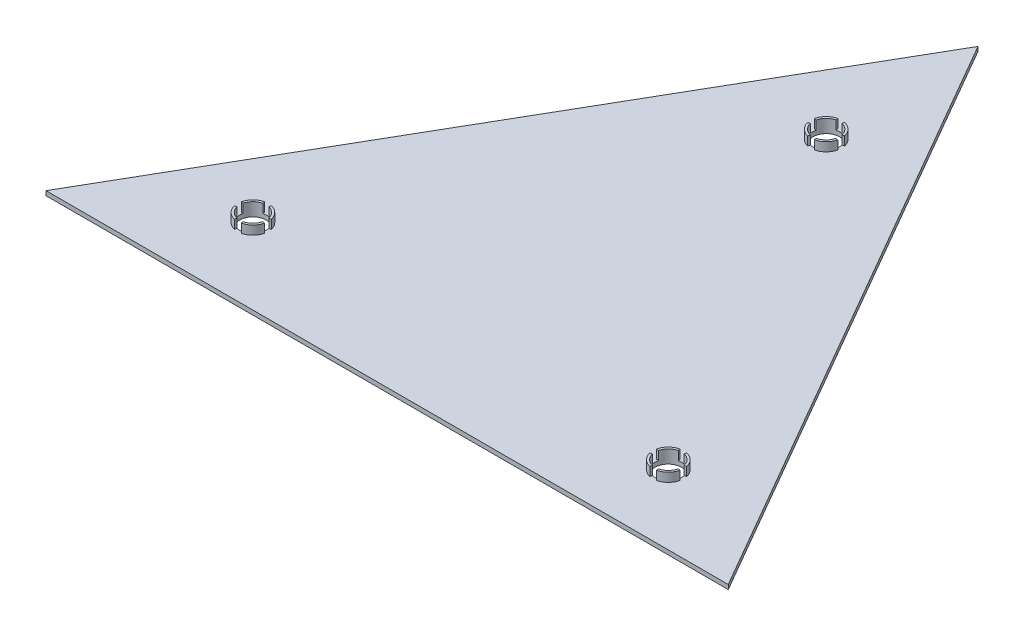
SolidWorks part; units mm, degrees
note: The reader was unsure of these and kept them because the rebuilt part matched: shared geometry of "Sketch1<15>".
ref_plane "Front Plane" through (0, 0, 0) normal (0, 0, 1) x (1, 0, 0)
ref_plane "Top Plane" through (0, 0, 0) normal (0, 1, 0) x (1, 0, 0)
ref_plane "Right Plane" through (0, 0, 0) normal (1, 0, 0) x (0, 0, -1)
sketch "Sketch1" plane through (0, 0, 0) normal (0, 1, 0) x (1, 0, 0)
  line L1 (363.2501, -12.5071) -> (363.2501, -12.0071) construction
  line L2 (363.2501, -12.0071) -> (364.0231, -12.0935) construction
  line L7 (364.0231, -12.0935) -> (363.9127, -12.5812)
  line L8 (363.2501, -12.0071) -> (362.4772, -12.0935) construction
  line L10 (362.4772, -12.0935) -> (362.5876, -12.5812)
  line L13 (366.2501, -15.5071) -> (366.7501, -15.5071) construction
  line L17 (360.2501, -15.5071) -> (359.7501, -15.5071) construction
  line L18 (363.2501, -18.5071) -> (363.2501, -19.0071) construction
  line L23 (366.7501, -15.5071) -> (366.6637, -14.7342) construction
  line L24 (366.7501, -15.5071) -> (366.6637, -16.2801) construction
  line L33 (359.7501, -15.5071) -> (359.8366, -14.7342) construction
  line L38 (359.7501, -15.5071) -> (359.8366, -16.2801) construction
  line L42 (363.2501, -19.0071) -> (364.0231, -18.9207) construction
  line L44 (363.2501, -19.0071) -> (362.4772, -18.9207) construction
  line L49 (359.8366, -14.7342) -> (363.2501, -15.5071) construction
  line L50 (363.2501, -15.5071) -> (366.6637, -14.7342) construction
  line L55 (359.8366, -16.2801) -> (363.2501, -15.5071) construction
  line L56 (363.2501, -15.5071) -> (366.6637, -16.2801) construction
  line L60 (362.4772, -18.9207) -> (363.2501, -15.5071) construction
  line L61 (363.2501, -15.5071) -> (364.0231, -18.9207) construction
  line L62 (359.8366, -14.7342) -> (360.3242, -14.8446)
  line L63 (359.8366, -16.2801) -> (360.3242, -16.1697)
  line L65 (362.4772, -18.9207) -> (362.5876, -18.433)
  line L69 (364.0231, -18.9207) -> (363.9127, -18.433)
  line L70 (366.6637, -14.7342) -> (366.1761, -14.8446)
  line L71 (366.6637, -16.2801) -> (366.1761, -16.1697)
  line L72 (410.2724, -94.8364) -> (410.2724, -98.3364) construction
  line L73 (410.2724, -98.3364) -> (406.7724, -98.3364) construction
  line L74 (406.7724, -98.3364) -> (406.8588, -97.5635) construction
  line L75 (413.7724, -98.3364) -> (410.2724, -98.3364) construction
  line L76 (410.2724, -98.3364) -> (410.2724, -101.8364) construction
  line L77 (410.2724, -101.8364) -> (411.0453, -101.75) construction
  line L78 (410.2724, -94.8364) -> (411.0453, -94.9228) construction
  line L79 (410.2724, -94.8364) -> (409.4994, -94.9228) construction
  line L80 (413.686, -97.5635) -> (413.7724, -98.3364) construction
  line L81 (413.7724, -98.3364) -> (413.686, -99.1094) construction
  line L82 (406.8588, -99.1094) -> (406.7724, -98.3364) construction
  line L83 (409.4994, -101.75) -> (410.2724, -101.8364) construction
  line L84 (409.4994, -94.9228) -> (410.2724, -98.3364) construction
  line L85 (410.2724, -98.3364) -> (411.0453, -94.9228) construction
  line L86 (406.8588, -99.1094) -> (410.2724, -98.3364) construction
  line L87 (410.2724, -98.3364) -> (406.8588, -97.5635) construction
  line L88 (413.686, -97.5635) -> (410.2724, -98.3364) construction
  line L89 (410.2724, -98.3364) -> (413.686, -99.1094) construction
  line L90 (409.4994, -101.75) -> (410.2724, -98.3364) construction
  line L91 (410.2724, -98.3364) -> (411.0453, -101.75) construction
  line L92 (409.4994, -94.9228) -> (409.6098, -95.4105)
  line L93 (411.0453, -94.9228) -> (410.9349, -95.4105)
  line L94 (413.686, -97.5635) -> (413.1983, -97.6739)
  line L95 (413.686, -99.1094) -> (413.1983, -98.999)
  line L96 (411.0453, -101.75) -> (410.9349, -101.2623)
  line L97 (409.4994, -101.75) -> (409.6098, -101.2623)
  line L98 (406.8588, -99.1094) -> (407.3465, -98.999)
  line L99 (406.8588, -97.5635) -> (407.3483, -97.6657)
  line L100 (314.6038, -93.3853) -> (314.6038, -96.8853) construction
  line L101 (314.6038, -96.8853) -> (318.1038, -96.8853) construction
  line L102 (314.6038, -100.3853) -> (314.6038, -96.8853) construction
  line L103 (314.6038, -96.8853) -> (311.1038, -96.8853) construction
  line L104 (314.6038, -96.8853) -> (313.8308, -93.4717) construction
  line L105 (313.8308, -93.4717) -> (314.6038, -93.3853) construction
  line L106 (314.6038, -93.3853) -> (315.3767, -93.4717) construction
  line L107 (315.3767, -93.4717) -> (314.6038, -96.8853) construction
  line L108 (314.6038, -96.8853) -> (318.0173, -96.1123) construction
  line L109 (318.0173, -96.1123) -> (318.1038, -96.8853) construction
  line L110 (318.1038, -96.8853) -> (318.0173, -97.6582) construction
  line L111 (318.0173, -97.6582) -> (314.6038, -96.8853) construction
  line L112 (314.6038, -96.8853) -> (315.3767, -100.2989) construction
  line L113 (315.3767, -100.2989) -> (314.6038, -100.3853) construction
  line L114 (314.6038, -100.3853) -> (313.8308, -100.2989) construction
  line L115 (313.8308, -100.2989) -> (314.6038, -96.8853) construction
  line L116 (314.6038, -96.8853) -> (311.1902, -97.6582) construction
  line L117 (311.1902, -97.6582) -> (311.1038, -96.8853) construction
  line L118 (311.1038, -96.8853) -> (311.1902, -96.1123) construction
  line L119 (311.1902, -96.1123) -> (314.6038, -96.8853) construction
  line L120 (311.1902, -96.1123) -> (311.6778, -96.2227)
  line L121 (311.1902, -97.6582) -> (311.6778, -97.5478)
  line L122 (313.8308, -100.2989) -> (313.9412, -99.8112)
  line L123 (315.3767, -100.2989) -> (315.2663, -99.8112)
  line L124 (318.0173, -97.6582) -> (317.5297, -97.5478)
  line L125 (318.0173, -96.1123) -> (317.5297, -96.2227)
  line L126 (315.3767, -93.4717) -> (315.2663, -93.9593)
  line L127 (313.8308, -93.4717) -> (313.9412, -93.9593)
  line L131 (284.8521, -114.0721) -> (362.2225, 19.9652)
  line L138 (439.5983, -114.0602) -> (362.2225, 19.9652)
  line L139 (284.8521, -114.0721) -> (439.5983, -114.0602)
  circle A0 centre (363.2501, -15.5071) radius 3.5
  circle A1 centre (410.2724, -98.3364) radius 3.5
  circle A2 centre (314.6038, -96.8853) radius 3.5
  circle A3 centre (363.2501, -15.5071) radius 3
  circle A4 centre (410.2724, -98.3364) radius 3
  circle A5 centre (314.6038, -96.8853) radius 3
  dimension "D1" = 6
  dimension "D2" = 7
  dimension "D3" = 6
  dimension "D4" = 7
  dimension "D5" = 6
  dimension "D6" = 7
extrude "Boss-Extrude3" add sketch "Sketch1" along normal blind 1
extrude "Boss-Extrude4" add sketch "Sketch1<15>" along normal blind 3 contours A5 L123 A2 L124 | A5 L125 A2 L126 | A5 L121 A2 L122 | A5 L127 A2 L120 | A4 L98 A1 L97 | A4 L96 A1 L95 | A4 L94 A1 L93 | A4 L92 A1 L99 | A3 L63 A0 L65 | A3 L69 A0 L71 | A3 L10 A0 L62 | A3 L70 A0 L7
sketch "Sketch1<15>" plane through (0, 0, 0) normal (0, 1, 0) x (1, 0, 0) same geometry as "Sketch1"
